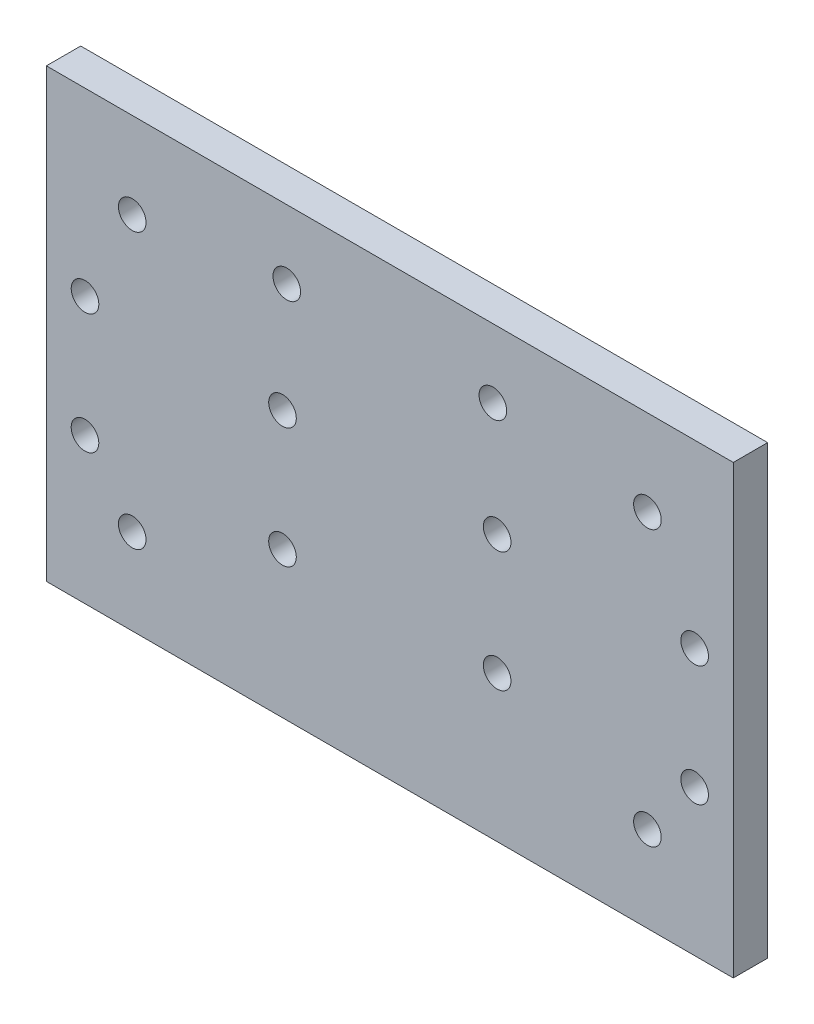
SolidWorks part; units mm, degrees
material "6061 Alloy"
ref_plane "Front Plane" through (0, 0, 0) normal (0, 0, 1) x (1, 0, 0)
ref_plane "Top Plane" through (0, 0, 0) normal (0, 1, 0) x (1, 0, 0)
ref_plane "Right Plane" through (0, 0, 0) normal (1, 0, 0) x (0, 0, -1)
sketch "Sketch1" plane through (0, 0, 0) normal (0, 0, 1) x (1, 0, 0)
  line L1 (-63.5, 41.275) -> (63.5, 41.275)
  line L2 (-63.5, 41.275) -> (-63.5, -41.275)
  line L3 (-63.5, -41.275) -> (63.5, -41.275)
  line L4 (63.5, 41.275) -> (63.5, -41.275)
  line L5 (-63.5, 41.275) -> (63.5, -41.275) construction
  line L6 (-63.5, -41.275) -> (63.5, 41.275) construction
  point P0 (0, 0)
  dimension "D1" = 127
  dimension "D2" = 82.55
extrude "Boss-Extrude1" add sketch "Sketch1" along normal blind 6.35
hole_wizard "Tapped Hole for #10-32 Helicoil1" positions "Sketch3" profile "Sketch4" tap size "#10-32" standard "Helicoil® Inch" end condition up to next
sketch "Sketch3" plane through (0, 0, 0) normal (0, 0, -1) x (-1, 0, 0)
  line L1 (-56.3565, 7.9375) -> (-19.844, 7.9375) construction
  line L2 (-56.3565, 7.9375) -> (-56.3565, -14.2875) construction
  line L3 (-56.3565, -14.2875) -> (-19.844, -14.2875) construction
  line L4 (-19.844, 7.9375) -> (-19.844, -14.2875) construction
  line L6 (19.844, 7.9375) -> (56.3565, 7.9375) construction
  line L7 (19.844, 7.9375) -> (19.844, -14.2875) construction
  line L8 (19.844, -14.2875) -> (56.3565, -14.2875) construction
  line L9 (56.3565, 7.9375) -> (56.3565, -14.2875) construction
  line L10 (0, 0) -> (0, -3.175) construction
  line L12 (-19.844, -3.175) -> (19.844, -3.175) construction
  line L13 (0, 0) -> (0, 28.575) construction
  line L15 (-19.05, 28.575) -> (19.05, 28.575) construction
  line L16 (63.5, -41.275) -> (-63.5, -41.275) construction
  point P0 (-56.3565, 7.9375)
  point P1 (-19.844, -14.2875)
  point P138 (-56.3565, -14.2875)
  point P139 (-19.844, 7.9375)
  point P140 (19.844, 7.9375)
  point P141 (56.3565, -14.2875)
  point P310 (19.844, -14.2875)
  point P311 (56.3565, 7.9375)
  point P347 (-19.05, 28.575)
  point P348 (19.05, 28.575)
  dimension "D1" = 22.225
  dimension "D2" = 36.5125
  dimension "D3" = 39.688
  dimension "D4" = 38.1
  dimension "D5" = 31.75
  dimension "D6" = 26.9875
sketch "Sketch4" plane through (56.3565, 7.9375, 0) normal (1, 0, 0) x (0, 1, 0)
  line L0 (0, 0) -> (0, 6.35)
  line L1 (0, 6.35) -> (2.5527, 6.35)
  line L2 (2.5527, 6.35) -> (2.5527, 0)
  line L5 (2.5527, 0) -> (0, 0)
  line L11 (0, -6.35) -> (0, 107.95) construction
  dimension "Thru Tap Drill Dia." = 5.1054
  dimension "Thru Tap Drill Depth" = 6.35
cosmetic thread "Hole Thread1" parameters "D1"=5.588, "D2"=5.936
cosmetic thread "Hole Thread2" parameters "D1"=5.588, "D2"=5.936
cosmetic thread "Hole Thread3" parameters "D1"=5.588, "D2"=5.936
cosmetic thread "Hole Thread4" parameters "D1"=5.588, "D2"=5.936
cosmetic thread "Hole Thread5" parameters "D1"=5.588, "D2"=5.936
cosmetic thread "Hole Thread6" parameters "D1"=5.588, "D2"=5.936
cosmetic thread "Hole Thread7" parameters "D1"=5.588, "D2"=5.936
cosmetic thread "Hole Thread8" parameters "D1"=5.588, "D2"=5.936
cosmetic thread "Hole Thread9" parameters "D1"=5.588, "D2"=5.936
cosmetic thread "Hole Thread10" parameters "D1"=5.588, "D2"=5.936
hole_wizard "Tapped Hole for #10-32 Helicoil2" positions "Sketch6" profile "Sketch5" tap size "#10-32" standard "Helicoil® Inch"
sketch "Sketch6" plane through (0, 0, 0) normal (0, 0, -1) x (-1, 0, 0)
  line L1 (-47.625, 25.4) -> (47.625, 25.4) construction
  line L2 (-47.625, 25.4) -> (-47.625, -25.4) construction
  line L3 (-47.625, -25.4) -> (47.625, -25.4) construction
  line L4 (47.625, 25.4) -> (47.625, -25.4) construction
  line L5 (-47.625, -25.4) -> (47.625, 25.4) construction
  point P0 (-47.625, 25.4)
  point P1 (47.625, -25.4)
  point P190 (-47.625, -25.4)
  point P191 (47.625, 25.4)
  dimension "D1" = 50.8
  dimension "D2" = 95.25
sketch "Sketch5" plane through (47.625, 25.4, 0) normal (1, 0, 0) x (0, 1, 0)
  line L0 (0, 0) -> (0, 13.4718)
  line L1 (0, 13.4718) -> (2.5527, 11.938)
  line L2 (2.5527, 11.938) -> (2.5527, 0)
  line L5 (2.5527, 0) -> (0, 0)
  line L10 (0, 13.4718) -> (-2.5527, 11.938) construction
  line L11 (0, -6.35) -> (0, 107.95) construction
  dimension "Tap Drill Dia." = 5.1054
  dimension "Tap Drill Depth" = 11.938
  dimension "Drill Angle" = 118
cosmetic thread "Hole Thread13" parameters "D1"=5.588, "D2"=5.936
cosmetic thread "Hole Thread14" parameters "D1"=5.588, "D2"=5.936
cosmetic thread "Hole Thread15" parameters "D1"=5.588, "D2"=5.936
cosmetic thread "Hole Thread16" parameters "D1"=5.588, "D2"=5.936
ref_plane "Plane1" through (0, -25.4, 0) normal (0, -1, 0) x (-1, 0, 0)
ref_plane "Plane2" through (0, 25.4, 0) normal (0, -1, 0) x (-1, 0, 0)
